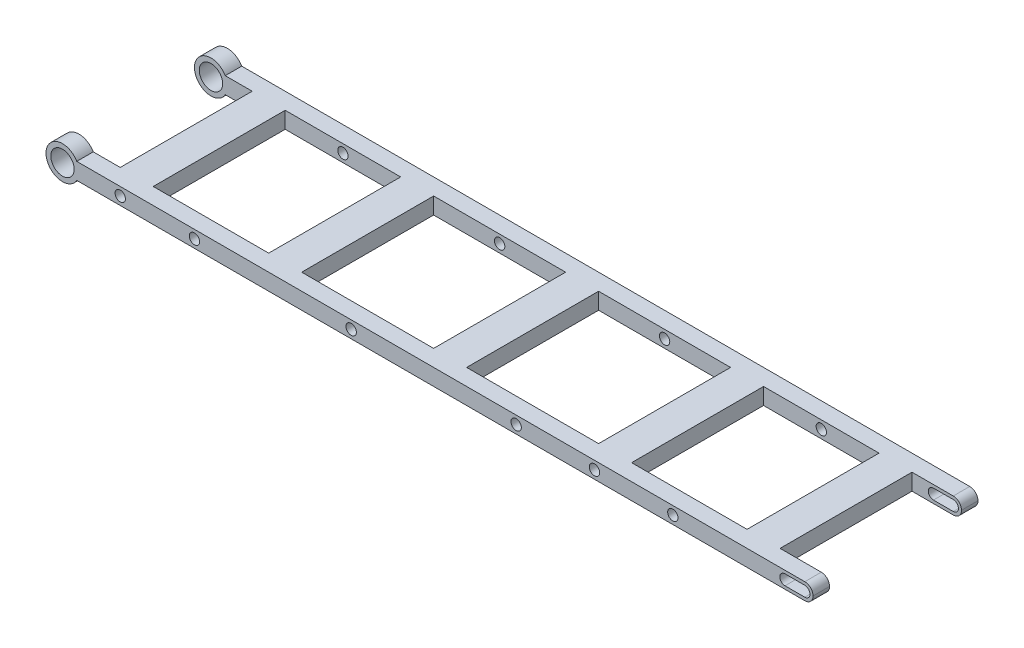
SolidWorks part; units mm, degrees
ref_plane "Front Plane" through (0, 0, 0) normal (0, 0, 1) x (1, 0, 0)
ref_plane "Top Plane" through (0, 0, 0) normal (0, 1, 0) x (1, 0, 0)
ref_plane "Right Plane" through (0, 0, 0) normal (1, 0, 0) x (0, 0, -1)
sketch "Sketch1" plane through (0, 0, 0) normal (0, 1, 0) x (1, 0, 0)
  line L0 (-146.05, 25.4) -> (-127, 25.4)
  line L1 (-146.05, 31.75) -> (146.05, 31.75)
  line L2 (-146.05, 31.75) -> (-146.05, 25.4)
  line L3 (-146.05, -31.75) -> (146.05, -31.75)
  line L4 (146.05, 31.75) -> (146.05, 25.4)
  line L5 (-146.05, 31.75) -> (146.05, -31.75) construction
  line L6 (-146.05, -31.75) -> (146.05, 31.75) construction
  line L8 (-146.05, -25.4) -> (-127, -25.4)
  line L10 (0, 31.75) -> (0, -31.75) construction
  line L11 (-6.35, 25.4) -> (-6.35, -25.4)
  line L12 (127, 25.4) -> (127, -25.4)
  line L14 (-6.35, 31.75) -> (-6.35, -31.75) construction
  line L15 (-57.15, 25.4) -> (-57.15, -25.4)
  line L20 (-69.85, 25.4) -> (-69.85, -25.4)
  line L21 (-114.3, 25.4) -> (-114.3, -25.4)
  line L22 (-127, 25.4) -> (-127, -25.4)
  line L23 (-146.05, -25.4) -> (-146.05, -31.75)
  line L24 (146.05, -25.4) -> (146.05, -31.75)
  line L32 (-114.3, 25.4) -> (-69.85, 25.4)
  line L33 (-114.3, -25.4) -> (-69.85, -25.4)
  line L36 (-57.15, -25.4) -> (-6.35, -25.4)
  line L38 (-57.15, 25.4) -> (-6.35, 25.4)
  line L47 (127, -25.4) -> (146.05, -25.4)
  line L48 (127, 25.4) -> (146.05, 25.4)
  line L50 (57.15, 25.4) -> (6.35, 25.4)
  line L51 (6.35, 25.4) -> (6.35, -25.4)
  line L52 (57.15, -25.4) -> (6.35, -25.4)
  line L53 (57.15, 25.4) -> (57.15, -25.4)
  line L54 (114.3, 25.4) -> (69.85, 25.4)
  line L55 (69.85, 25.4) -> (69.85, -25.4)
  line L56 (114.3, -25.4) -> (69.85, -25.4)
  line L57 (114.3, 25.4) -> (114.3, -25.4)
  point P0 (0, 0)
  dimension "D1" = 63.5
  dimension "D2" = 292.1
  dimension "D4" = 6.35
  dimension "D3" = 6.35
  dimension "D14" = 6.35
  dimension "D5" = 19.05
  dimension "D7" = 44.45
  dimension "D8" = 19.05
  dimension "D6" = 50.8
  dimension "D13" = 12.7
extrude "Boss-Extrude1" add sketch "Sketch1" against normal blind 6.35
fillet "Fillet2" radius 3.175 8 edges at (-146.05, -6.35, 28.575) (-146.05, 0, 28.575) (-146.05, -6.35, -28.575) (-146.05, 0, -28.575) (146.05, -6.35, -28.575) (146.05, 0, -28.575) (146.05, -6.35, 28.575) (146.05, 0, 28.575)
sketch "Sketch2" plane through (0, 0, 31.75) normal (0, 0, 1) x (1, 0, 0)
  line L0 (-142.875, 0) -> (-142.875, -6.35) construction
  line L1 (0, 0) -> (0, -6.35) construction
  line L2 (-114.3, 0) -> (-69.85, 0) construction
  line L3 (-114.3, 0) -> (-69.85, 0)
  line L4 (142.875, 0) -> (-142.875, 0)
  line L5 (-57.15, 0) -> (-6.35, 0) construction
  line L6 (-142.875, -6.35) -> (142.875, -6.35)
  line L7 (-57.15, 0) -> (-6.35, 0)
  line L8 (142.875, 0) -> (-142.875, 0)
  line L10 (-142.875, -6.35) -> (142.875, -6.35)
  line L16 (-31.75, 0) -> (-31.75, -6.35) construction
  line L17 (-92.075, 0) -> (-92.075, -6.35) construction
  line L19 (135.255, -1.1811) -> (142.875, -1.1811)
  line L20 (31.75, 0) -> (31.75, -6.35) construction
  line L21 (135.255, -5.1689) -> (142.875, -5.1689)
  line L22 (92.075, 0) -> (92.075, -6.35) construction
  line L23 (-127, 0) -> (-142.875, 0) construction
  line L24 (-127, 0) -> (-142.875, 0)
  line L25 (-127, 0) -> (-114.3, 0)
  line L26 (31.75, -3.175) -> (92.075, -3.175)
  circle A0 centre (-142.875, -3.175) radius 6.35
  circle A5 centre (-142.875, -3.175) radius 4.4996
  circle A6 centre (-92.075, -3.175) radius 1.9939
  circle A15 centre (-31.75, -3.175) radius 1.9939
  circle A16 centre (31.75, -3.175) radius 1.9939
  circle A17 centre (92.075, -3.175) radius 1.9939
  arc A19 (-142.875, 0) -> (-146.05, -3.175) centre (-142.875, -3.175) ccw
  arc A20 (-142.875, 0) -> (-146.05, -3.175) centre (-142.875, -3.175) ccw
  arc A21 (-146.05, -3.175) -> (-142.875, -6.35) centre (-142.875, -3.175) ccw
  arc A22 (-146.05, -3.175) -> (-142.875, -6.35) centre (-142.875, -3.175) ccw
  arc A23 (142.875, -6.35) -> (146.05, -3.175) centre (142.875, -3.175) ccw
  arc A24 (142.875, -6.35) -> (146.05, -3.175) centre (142.875, -3.175) ccw
  arc A25 (146.05, -3.175) -> (142.875, 0) centre (142.875, -3.175) ccw
  arc A26 (146.05, -3.175) -> (142.875, 0) centre (142.875, -3.175) ccw
  arc A27 (142.875, -5.1689) -> (142.875, -1.1811) centre (142.875, -3.175) ccw
  arc A28 (135.255, -1.1811) -> (135.255, -5.1689) centre (135.255, -3.175) ccw
  circle A29 centre (-120.65, -3.175) radius 1.9939
  circle A30 centre (61.9125, -3.175) radius 1.9939
  point P15 (-92.075, 0)
  point P45 (0, 0)
  point P46 (61.9125, -3.175)
  point P48 (110.2603, -3.175)
  dimension "D1" = 12.7
  dimension "D4" = 3.9878
  dimension "D5" = 3.9878
  dimension "D6" = 31.75
  dimension "D7" = 92.075
  dimension "D11" = 8.9992
  dimension "D12" = 3.9878
  dimension "D13" = 3.9878
  dimension "D14" = 22.225
  dimension "D15" = 3.9878
  dimension "D3" = 3.9878
  dimension "D8" = 3.9878
  dimension "D10" = 7.62
  dimension "D9" = 3.9878
  dimension "D2" = 0
extrude "Boss-Extrude3" add sketch "Sketch2" along direction (0, 0, -1) on the side against the normal up to surface (6.35 mm away) contours A0 up to face at (-137.423, -3.175, 25.4)
sketch "Sketch4" plane through (0, 0, -31.75) normal (0, 0, -1) x (-1, 0, 0)
  circle A0 centre (142.875, -3.175) radius 6.35 construction
  circle A1 centre (142.875, -3.175) radius 6.35
extrude "Boss-Extrude4" add sketch "Sketch4" against normal up to surface (6.35 mm away) up to face at (-137.423, -3.175, -25.4)
extrude "Cut-Extrude1" cut sketch "Sketch2<4>" against normal up to surface (63.5 mm away) contours L19 A28 L21 A27 | A5 | A6 | A15 | A16 | A17 | A29 | A30 region at (139.065, -3.175, 31.75) up to face at (29.3029, -3.175, -31.75)
sketch "Sketch2<4>" plane through (0, 0, 31.75) normal (0, 0, 1) x (1, 0, 0) same geometry as "Sketch2"
